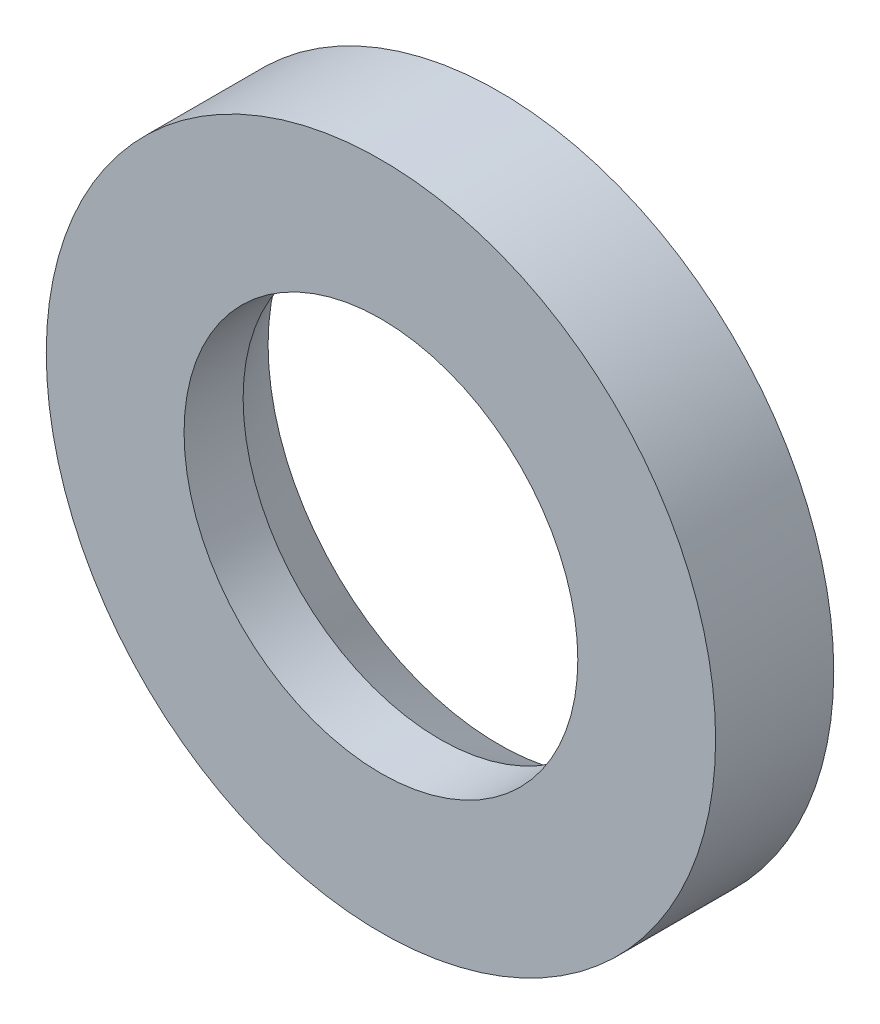
SolidWorks part; units mm, degrees
ref_plane "Front Plane" through (0, 0, 0) normal (0, 0, 1) x (1, 0, 0)
ref_plane "Top Plane" through (0, 0, 0) normal (0, 1, 0) x (1, 0, 0)
ref_plane "Right Plane" through (0, 0, 0) normal (1, 0, 0) x (0, 0, -1)
sketch "Sketch1" plane through (0, 0, 0) normal (0, 0, 1) x (1, 0, 0)
  circle A0 centre (0, 0) radius 1.7
  dimension "D1" = 3.4
extrude "Boss-Extrude1" add sketch "Sketch1" against normal blind 0.6
sketch "Sketch2" plane through (0, 0, 0) normal (0, 0, 1) x (1, 0, 0)
  circle A0 centre (0, 0) radius 1
  dimension "D1" = 2
extrude "Cut-Extrude1" cut sketch "Sketch2" against normal through all
chamfer "Chamfer1" distance 0.3 angle 30 1 edges at (1, 0, -0.6) first distance on face at (1, 0, -0.6)
